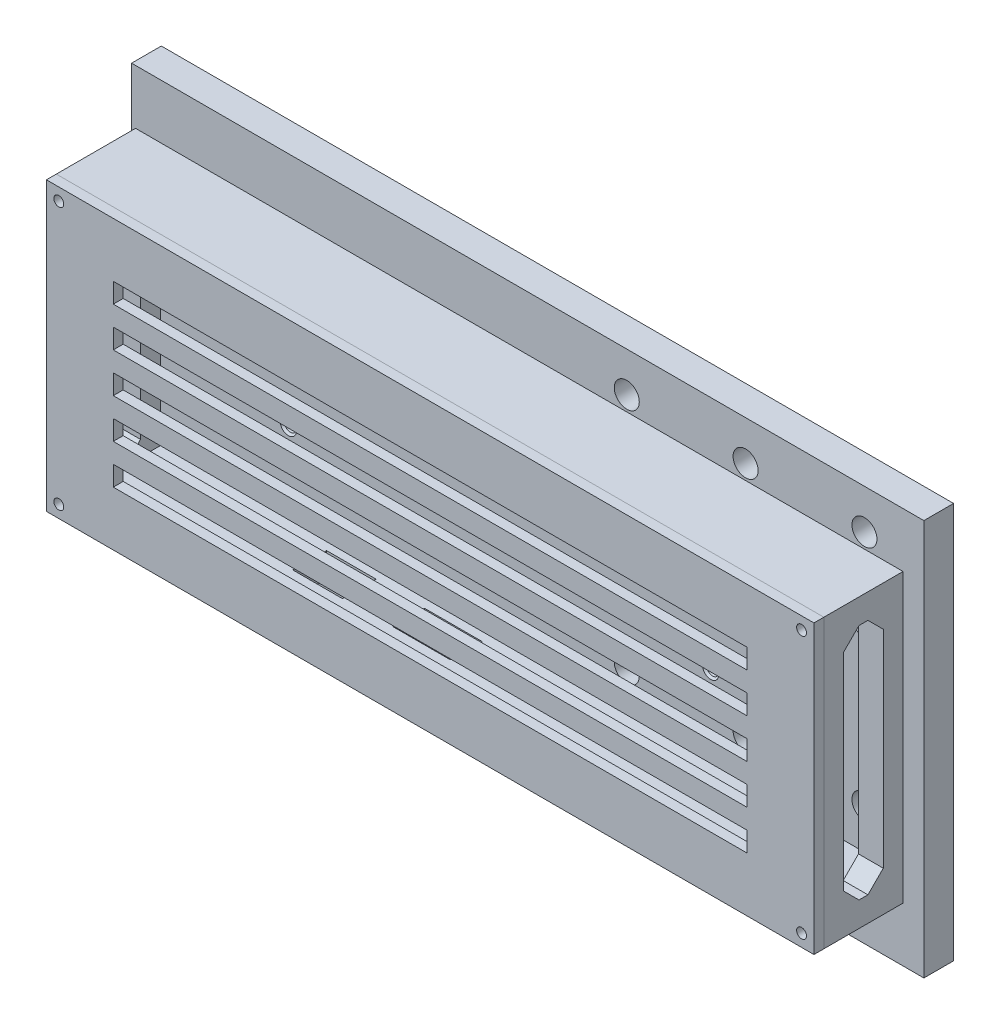
SolidWorks part; units mm, degrees
ref_plane "Front Plane" through (0, 0, 0) normal (0, 0, 1) x (1, 0, 0)
ref_plane "Top Plane" through (0, 0, 0) normal (0, 1, 0) x (1, 0, 0)
ref_plane "Right Plane" through (0, 0, 0) normal (1, 0, 0) x (0, 0, -1)
sketch "Sketch1" plane through (0, 0, 0) normal (0, 0, 1) x (1, 0, 0)
  line L1 (-127, 63.5) -> (127, 63.5)
  line L2 (-127, 63.5) -> (-127, -63.5)
  line L3 (-127, -63.5) -> (127, -63.5)
  line L4 (127, 63.5) -> (127, -63.5)
  line L5 (-127, 63.5) -> (127, -63.5) construction
  line L6 (-127, -63.5) -> (127, 63.5) construction
  point P0 (0, 0)
  dimension "D1" = 127
  dimension "D2" = 254
extrude "base" add sketch "Sketch1" along normal blind 9.525
hole_wizard "O (0.316) Diameter Hole1" positions "Sketch2" profile "Sketch3" hole size "O" standard "ANSI Inch" end condition up to next
sketch "Sketch2" plane through (0, 0, 9.525) normal (0, 0, 1) x (1, 0, 0)
  line L0 (107.95, -25.4) -> (107.95, -50.8)
  line L1 (69.85, -50.8) -> (69.85, -25.4)
  line L2 (31.75, -25.4) -> (31.75, -50.8)
  line L3 (31.75, -38.1) -> (69.85, -38.1)
  line L4 (69.85, -38.1) -> (107.95, -38.1)
  line L5 (107.95, 25.4) -> (107.95, 50.8)
  line L6 (69.85, 50.8) -> (69.85, 25.4)
  line L7 (31.75, 25.4) -> (31.75, 50.8)
  line L9 (31.75, 38.1) -> (69.85, 38.1)
  line L10 (69.85, 38.1) -> (107.95, 38.1)
  line L11 (69.85, -25.4) -> (69.85, 25.4) construction
  line L12 (-127, 63.5) -> (-127, -63.5) construction
  line L13 (-127, 0) -> (69.85, 0) construction
  line L14 (69.85, 0) -> (127, 0) construction
  line L15 (127, -63.5) -> (127, 63.5) construction
  point P0 (31.75, 50.8)
  point P2 (69.85, 50.8)
  point P4 (107.95, 50.8)
  point P6 (107.95, 25.4)
  point P8 (69.85, 25.4)
  point P10 (31.75, 25.4)
  point P12 (31.75, -25.4)
  point P14 (31.75, -50.8)
  point P16 (69.85, -50.8)
  point P18 (69.85, -25.4)
  point P20 (107.95, -25.4)
  point P22 (107.95, -50.8)
  dimension "D1" = 57.15
  dimension "D2" = 76.2
  dimension "D3" = 38.1
  dimension "D4" = 25.4
sketch "Sketch3" plane through (31.75, 50.8, 9.525) normal (1, 0, 0) x (0, -1, 0)
  line L0 (0, 0) -> (0, 9.525)
  line L1 (0, 9.525) -> (4.0132, 9.525)
  line L2 (4.0132, 9.525) -> (4.0132, 0)
  line L5 (4.0132, 0) -> (0, 0)
  line L11 (0, -6.35) -> (0, 107.95) construction
  dimension "Thru Hole Dia." = 8.0264
  dimension "Thru Hole Depth" = 9.525
sketch "Sketch4" plane through (0, 0, 9.525) normal (0, 0, 1) x (1, 0, 0)
  line L0 (58.6422, 31.242) -> (-76.7398, -12.192) construction
  line L1 (-125.73, 46.0375) -> (120.3325, 46.0375)
  line L2 (-125.73, 46.0375) -> (-125.73, -46.0375)
  line L3 (-125.73, -46.0375) -> (120.3325, -46.0375)
  line L4 (120.3325, 46.0375) -> (120.3325, -46.0375)
  line L5 (120.3325, 0) -> (112.395, 0) construction
  line L6 (-117.7925, 0) -> (-125.73, 0) construction
  line L7 (-117.7925, 38.1) -> (112.395, 38.1)
  line L8 (-117.7925, 38.1) -> (-117.7925, -38.1)
  line L9 (-117.7925, -38.1) -> (112.395, -38.1)
  line L10 (112.395, 38.1) -> (112.395, -38.1)
  line L11 (-117.7925, 38.1) -> (112.395, -38.1) construction
  line L12 (-117.7925, -38.1) -> (112.395, 38.1) construction
  line L13 (58.6422, -12.192) -> (-76.7398, 31.242) construction
  line L14 (-2.6988, 38.1) -> (-2.6988, 46.0375) construction
  line L15 (-79.6925, 34.925) -> (61.595, 34.925) construction
  line L16 (-79.6925, 34.925) -> (-79.6925, -15.875) construction
  line L17 (-79.6925, -15.875) -> (61.595, -15.875) construction
  line L18 (61.595, 34.925) -> (61.595, -15.875) construction
  line L19 (-79.6925, 34.925) -> (61.595, -15.875) construction
  line L20 (-79.6925, -15.875) -> (61.595, 34.925) construction
  line L21 (-2.6988, -46.0375) -> (-2.6988, -38.1) construction
  line L22 (-2.6988, -38.1) -> (-2.6988, -15.875) construction
  line L23 (-2.6988, 38.1) -> (-2.6988, 34.925) construction
  line L24 (-127, 63.5) -> (-127, -63.5) construction
  point P5 (-2.6988, 0)
  point P7 (0, 0)
  point P11 (-76.7398, 31.242)
  point P12 (-76.7398, -12.192)
  point P13 (58.6422, -12.192)
  point P14 (58.6422, 31.242)
  point P19 (-9.0488, 9.525)
  point P20 (-9.0488, 9.525)
  point P23 (0, 0)
  point P34 (-9.0488, 9.525)
  dimension "D1" = 43.434
  dimension "D2" = 135.382
  dimension "D3" = 7.9375
  dimension "D4" = 50.8
  dimension "D5" = 141.2875
  dimension "D6" = 3.175
  dimension "D7" = 38.1
  dimension "D8" = 50.8
  dimension "D9" = 1.27
  dimension "D10" = 22.225
extrude "Boss-Extrude2" add sketch "Sketch4" along normal blind 25.4
hole_wizard "#23 (0.154) Diameter Hole1" positions "Sketch6" profile "Sketch7" hole size "#23" standard "ANSI Inch" end condition up to next
sketch "Sketch6" plane through (0, 0, 9.525) normal (0, 0, 1) x (1, 0, 0)
  line L0 (84.0422, 32.258) -> (84.0422, -13.208) construction
  line L1 (58.6422, 31.242) -> (58.6422, -12.192) construction
  line L2 (58.6422, 9.525) -> (84.0422, 9.525) construction
  point P13 (84.0422, 32.258)
  point P15 (84.0422, -13.208)
  point P30 (-76.7398, 31.242)
  point P33 (58.6422, 31.242)
  point P36 (58.6422, -12.192)
  point P39 (-76.7398, -12.192)
  dimension "D1" = 45.466
  dimension "D2" = 25.4
sketch "Sketch7" plane through (84.0422, 32.258, 9.525) normal (1, 0, 0) x (0, -1, 0)
  line L0 (0, 0) -> (0, 9.525)
  line L1 (0, 9.525) -> (1.9558, 9.525)
  line L2 (1.9558, 9.525) -> (1.9558, 0.635)
  line L3 (1.9558, 0.635) -> (2.5908, 0)
  line L5 (2.5908, 0) -> (0, 0)
  line L6 (-1.9558, 0.635) -> (-2.5908, 0) construction
  line L11 (0, -6.35) -> (0, 107.95) construction
  dimension "Thru Hole Dia." = 3.9116
  dimension "Thru Hole Depth" = 9.525
  dimension "Near C'Sink Dia." = 5.1816
  dimension "Near C'Sink Angle" = 90
hole_wizard "#23 (0.154) Diameter Hole2" positions "Sketch8" profile "Sketch10" hole size "#23" standard "ANSI Inch"
sketch "Sketch8" plane through (0, 0, 34.925) normal (0, 0, 1) x (1, 0, 0)
  line L2 (112.395, 38.1) -> (120.3325, 46.0375) construction
  line L3 (112.395, -38.1) -> (120.3325, -46.0375) construction
  line L4 (-117.7925, -38.1) -> (-125.73, -46.0375) construction
  line L5 (-125.73, 46.0375) -> (-117.7925, 38.1) construction
  line L6 (112.395, 38.1) -> (-117.7925, 38.1) construction
  line L7 (-117.7925, 38.1) -> (-117.7925, -38.1) construction
  point P0 (-121.7613, 42.0687)
  point P2 (-121.7613, -42.0687)
  point P4 (116.3637, -42.0687)
  point P6 (116.3637, 42.0687)
  point P35 (0, 0)
  point P36 (116.3637, -42.0687)
sketch "Sketch10" plane through (-121.7613, 42.0687, 34.925) normal (1, 0, 0) x (0, -1, 0)
  line L0 (0, 0) -> (0, 13.8752)
  line L1 (0, 13.8752) -> (1.9558, 12.7)
  line L2 (1.9558, 12.7) -> (1.9558, 0.635)
  line L3 (1.9558, 0.635) -> (2.5908, 0)
  line L5 (2.5908, 0) -> (0, 0)
  line L6 (-1.9558, 0.635) -> (-2.5908, 0) construction
  line L10 (0, 13.8752) -> (-1.9558, 12.7) construction
  line L11 (0, -6.35) -> (0, 107.95) construction
  dimension "Hole Dia." = 3.9116
  dimension "Hole Depth" = 12.7
  dimension "Near C'Sink Dia." = 5.1816
  dimension "Near C'Sink Angle" = 90
  dimension "Drill Angle" = 118
sketch "Sketch11" plane through (0, -46.0375, 0) normal (0, -1, 0) x (1, 0, 0)
  line L0 (-112.7125, 22.733) -> (-74.6125, 22.733) construction
  line L1 (-74.6125, 22.733) -> (-74.6125, 12.065) construction
  line L2 (-74.6125, 12.065) -> (-112.7125, 12.065) construction
  line L3 (-112.7125, 12.065) -> (-112.7125, 22.733) construction
  line L4 (-87.3125, 21.5265) -> (-100.0125, 21.5265)
  line L5 (-100.0125, 21.5265) -> (-100.0125, 13.2715)
  line L6 (-100.0125, 13.2715) -> (-87.3125, 13.2715)
  line L7 (-87.3125, 13.2715) -> (-87.3125, 21.5265)
  line L8 (-79.6925, 17.399) -> (-107.6325, 17.399) construction
  line L9 (-93.6625, 22.733) -> (-93.6625, 12.065) construction
  circle A0 centre (-79.6925, 17.399) radius 1.5875
  circle A1 centre (-107.6325, 17.399) radius 1.5875
  point P14 (-93.6625, 17.399)
  point P15 (-103.3319, 18.3513)
  point P16 (-93.6625, 17.399)
  point P17 (-87.3125, 17.399)
  point P18 (-93.6625, 21.5265)
  dimension "D1" = 27.94
  dimension "D6" = 3.175
  dimension "D2" = 10.668
  dimension "D3" = 38.1
  dimension "D4" = 8.255
  dimension "D5" = 12.7
  dimension "D7" = 5.08
  dimension "D8" = 2.54
extrude "usb connector" cut sketch "Sketch11" against normal up to next
sketch "Sketch13" plane through (0, -46.0375, 46.0375) normal (0, -1, 0) x (-1, 0, 0)
  line L0 (38.6056, 33.9725) -> (69.5936, 33.9725) construction
  line L1 (69.5936, 33.9725) -> (69.5936, 23.3045) construction
  line L2 (69.5936, 23.3045) -> (38.6056, 23.3045) construction
  line L3 (38.6056, 23.3045) -> (38.6056, 33.9725) construction
  line L4 (62.0371, 34.036) -> (46.1621, 34.036)
  line L5 (46.1621, 34.036) -> (46.1621, 23.241)
  line L6 (46.1621, 23.241) -> (62.0371, 23.241)
  line L7 (62.0371, 23.241) -> (62.0371, 34.036)
  line L8 (66.5964, 28.6385) -> (41.6028, 28.6385) construction
  line L9 (54.0996, 33.9725) -> (54.0996, 23.3045) construction
  line L10 (69.5936, 28.6385) -> (87.3125, 28.6385) construction
  line L11 (87.3125, 32.766) -> (87.3125, 24.511) construction
  circle A0 centre (66.5964, 28.6385) radius 1.5875
  circle A1 centre (41.6028, 28.6385) radius 1.5875
  point P14 (54.0996, 28.6385)
  point P16 (54.0996, 28.6385)
  point P17 (62.0371, 28.6385)
  point P18 (54.0996, 34.036)
  dimension "D1" = 24.9936
  dimension "D6" = 3.175
  dimension "D2" = 10.668
  dimension "D3" = 30.988
  dimension "D4" = 10.795
  dimension "D5" = 15.875
extrude "D-Sub connector" cut sketch "Sketch13" against normal up to next
sketch "Sketch14" plane through (0, -46.0375, 0) normal (0, -1, 0) x (1, 0, 0)
  line L0 (-30.2871, 22.479) -> (-30.2871, 12.319)
  line L1 (-30.2871, 12.319) -> (-11.9146, 12.319)
  line L2 (-11.9146, 12.319) -> (-8.9511, 15.2825)
  line L3 (-8.9511, 15.2825) -> (-8.9511, 19.5155)
  line L4 (-8.9511, 19.5155) -> (-11.9146, 22.479)
  line L5 (-11.9146, 22.479) -> (-30.2871, 22.479)
  line L6 (-30.2871, 17.399) -> (-46.1621, 17.399) construction
  line L7 (-46.1621, 12.0015) -> (-46.1621, 22.7965) construction
  point P0 (-8.9511, 17.399)
  point P8 (-30.2871, 17.399)
  dimension "D1" = 21.336
  dimension "D2" = 10.16
  dimension "D3" = 4.191
  dimension "D4" = 45
  dimension "D5" = 15.875
extrude "power input" cut sketch "Sketch14" against normal up to next
sketch "Sketch15" plane through (0, -46.0375, 0) normal (0, -1, 0) x (1, 0, 0)
  line L0 (18.3539, 17.399) -> (-0.6961, 17.399) construction
  line L1 (-0.6961, 17.399) -> (-8.9511, 17.399) construction
  line L2 (-8.9511, 15.2825) -> (-8.9511, 19.5155) construction
  circle A0 centre (-0.6961, 17.399) radius 3.55
  circle A1 centre (8.8289, 17.399) radius 3.55
  circle A2 centre (18.3539, 17.399) radius 3.55
  dimension "D1" = 7.1
  dimension "D2" = 19.05
  dimension "D3" = 8.255
extrude "motor output" cut sketch "Sketch15" against normal up to next
sketch "Sketch16" plane through (-125.73, 0, 0) normal (-1, 0, 0) x (0, 0, 1)
  line L0 (34.925, -46.0375) -> (9.525, -46.0375) construction
  line L1 (28.575, 38.1) -> (15.875, 38.1)
  line L2 (28.575, 38.1) -> (28.575, -38.1)
  line L3 (28.575, -38.1) -> (15.875, -38.1)
  line L4 (15.875, 38.1) -> (15.875, -38.1)
  line L5 (28.575, 38.1) -> (15.875, -38.1) construction
  line L6 (28.575, -38.1) -> (15.875, 38.1) construction
  line L7 (34.925, 46.0375) -> (34.925, -46.0375) construction
  point P0 (22.225, 0)
  point P5 (0, 0)
  point P8 (22.225, -46.0375)
  point P9 (0, 0)
  point P12 (34.925, 0)
  dimension "D1" = 76.2
  dimension "D2" = 12.7
extrude "Cut-Extrude5" cut sketch "Sketch16" against normal through all
chamfer "Chamfer1" distance 4.92 angle 45 8 edges at (116.3637, 38.1, 28.575) (116.3637, 38.1, 15.875) (116.3637, -38.1, 15.875) (116.3637, -38.1, 28.575) (-121.7613, -38.1, 28.575) (-121.7613, -38.1, 15.875) (-121.7613, 38.1, 15.875) (-121.7613, 38.1, 28.575)
sketch "Sketch17" plane through (0, 0, 34.925) normal (0, 0, 1) x (1, 0, 0)
  line L0 (120.3325, -46.0375) -> (120.3325, 46.0375) construction
  line L1 (120.3325, 46.0375) -> (-125.73, 46.0375)
  line L2 (120.3325, 46.0375) -> (120.3325, -46.0375)
  line L3 (120.3325, -46.0375) -> (-125.73, -46.0375)
  line L4 (-125.73, 46.0375) -> (-125.73, -46.0375)
  line L5 (120.3325, 46.0375) -> (-125.73, -46.0375) construction
  line L6 (120.3325, -46.0375) -> (-125.73, 46.0375) construction
  line L7 (120.3325, 46.0375) -> (-125.73, 46.0375) construction
  line L8 (-2.6988, -25.4) -> (-2.6988, -12.7) construction
  line L9 (98.9012, -28.575) -> (-104.2988, -28.575)
  line L10 (98.9012, -28.575) -> (98.9012, -22.225)
  line L11 (98.9012, -22.225) -> (-104.2988, -22.225)
  line L12 (-104.2988, -28.575) -> (-104.2988, -22.225)
  line L13 (98.9012, -28.575) -> (-104.2988, -22.225) construction
  line L14 (98.9012, -22.225) -> (-104.2988, -28.575) construction
  line L15 (98.9012, -15.875) -> (-104.2988, -15.875)
  line L16 (98.9012, -15.875) -> (98.9012, -9.525)
  line L17 (98.9012, -9.525) -> (-104.2988, -9.525)
  line L18 (-104.2988, -15.875) -> (-104.2988, -9.525)
  line L19 (98.9012, -15.875) -> (-104.2988, -9.525) construction
  line L20 (98.9012, -9.525) -> (-104.2988, -15.875) construction
  line L21 (98.9012, -3.175) -> (-104.2988, -3.175)
  line L22 (98.9012, -3.175) -> (98.9012, 3.175)
  line L23 (98.9012, 3.175) -> (-104.2988, 3.175)
  line L24 (-104.2988, -3.175) -> (-104.2988, 3.175)
  line L25 (98.9012, -3.175) -> (-104.2988, 3.175) construction
  line L26 (98.9012, 3.175) -> (-104.2988, -3.175) construction
  line L27 (98.9012, 9.525) -> (-104.2988, 9.525)
  line L28 (98.9012, 9.525) -> (98.9012, 15.875)
  line L29 (98.9012, 15.875) -> (-104.2988, 15.875)
  line L30 (-104.2988, 9.525) -> (-104.2988, 15.875)
  line L31 (98.9012, 9.525) -> (-104.2988, 15.875) construction
  line L32 (98.9012, 15.875) -> (-104.2988, 9.525) construction
  line L33 (98.9012, 22.225) -> (-104.2988, 22.225)
  line L34 (98.9012, 22.225) -> (98.9012, 28.575)
  line L35 (98.9012, 28.575) -> (-104.2988, 28.575)
  line L36 (-104.2988, 22.225) -> (-104.2988, 28.575)
  line L37 (98.9012, 22.225) -> (-104.2988, 28.575) construction
  line L38 (98.9012, 28.575) -> (-104.2988, 22.225) construction
  line L39 (-2.6988, -12.7) -> (-2.6988, 0) construction
  line L40 (-2.6988, 0) -> (-2.6988, 12.7) construction
  line L41 (-2.6988, 12.7) -> (-2.6988, 25.4) construction
  circle A0 centre (116.3637, -42.0687) radius 1.5875
  circle A1 centre (116.3637, 42.0687) radius 1.5875
  circle A2 centre (-121.7613, 42.0687) radius 1.5875
  circle A3 centre (-121.7613, -42.0687) radius 1.5875
  circle A5 centre (-121.7613, -42.0687) radius 1.9558 construction
  point P0 (-2.6988, 0)
  point P24 (-2.6988, -12.7)
  point P26 (-2.6988, -25.4)
  point P34 (-2.6988, 0)
  point P39 (-2.6988, 12.7)
  point P44 (-2.6988, 25.4)
  point P51 (-2.6988, -24.1474)
  dimension "D1" = 3.175
  dimension "D2" = 203.2
  dimension "D3" = 6.35
  dimension "D4" = 12.7
extrude "Boss-Extrude3" add sketch "Sketch17" along normal blind 3.175 separate body
